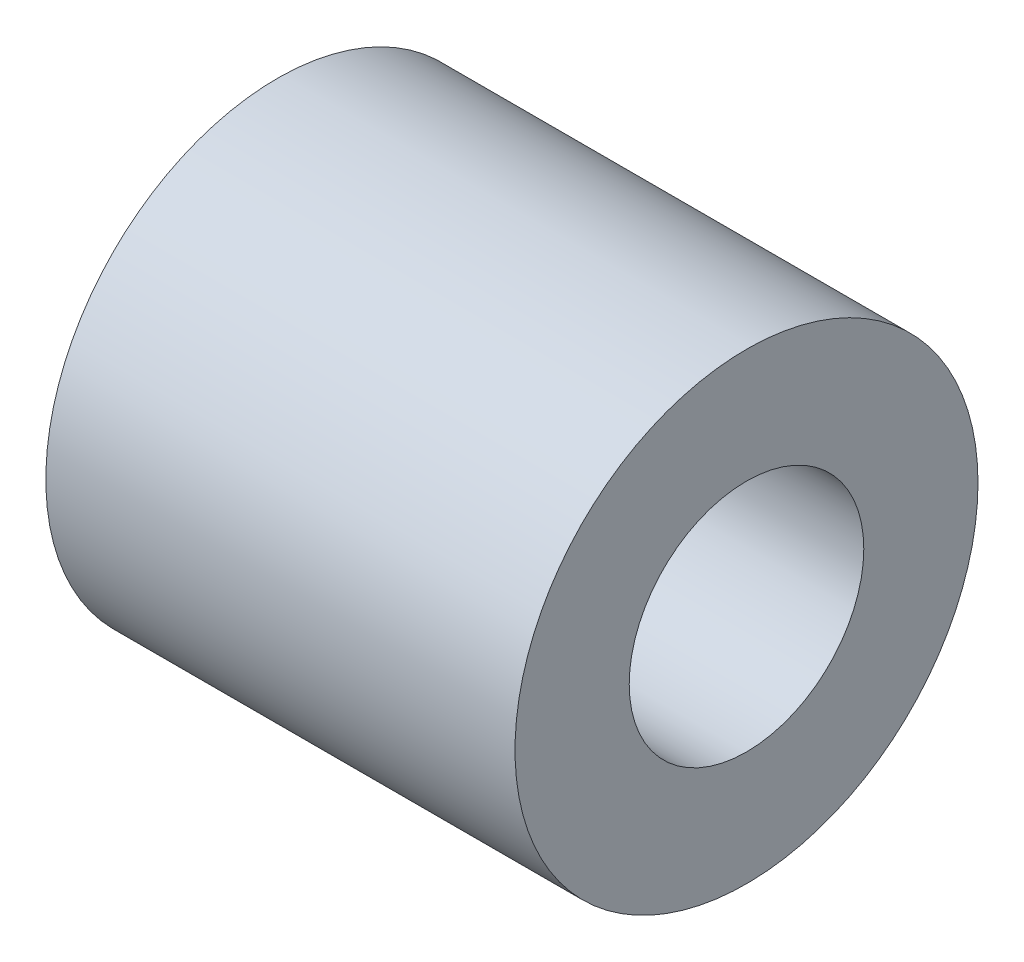
SolidWorks part; units mm, degrees
ref_plane "Front" through (0, 0, 0) normal (0, 0, 1) x (1, 0, 0)
ref_plane "Top" through (0, 0, 0) normal (0, 1, 0) x (1, 0, 0)
ref_plane "Right" through (0, 0, 0) normal (1, 0, 0) x (0, 0, -1)
sketch "Sketch1" plane through (0, 0, 0) normal (1, 0, 0) x (0, 0, -1)
  circle A0 centre (0, 0) radius 2.413
  circle A1 centre (0, 0) radius 4.7625
  dimension "D1" = 4.826
  dimension "D2" = 9.525
extrude "Boss-Extrude1" add sketch "Sketch1" along normal mid plane 9.652
